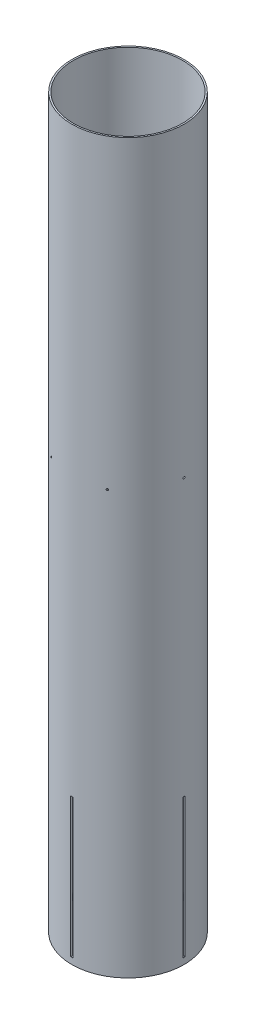
SolidWorks part; units mm, degrees
material "A-Glass Fiber"
ref_plane "Front Plane" through (0, 0, 0) normal (0, 0, 1) x (1, 0, 0)
ref_plane "Top Plane" through (0, 0, 0) normal (0, 1, 0) x (1, 0, 0)
ref_plane "Right Plane" through (0, 0, 0) normal (1, 0, 0) x (0, 0, -1)
sketch "Sketch1" plane through (0, 0, 0) normal (0, 1, 0) x (1, 0, 0)
  circle A0 centre (0, 0) radius 76.2
  circle A1 centre (0, 0) radius 78.359
  dimension "D1" = 152.4
  dimension "D2" = 156.718
extrude "Boss-Extrude1" add sketch "Sketch1" along normal blind 1016
ref_plane "Plane1" through (0, 0, 0) normal (0.7071, 0, 0.7071) x (0.7071, 0, -0.7071)
ref_axis "Axis1" through (0, 1016, 0) along (0, -1, 0)
sketch "Sketch2" plane through (0, 0, 0) normal (1, 0, 0) x (0, 0, -1)
  line L0 (0, 0) -> (0, 8.89)
  line L1 (1.5875, 8.89) -> (-1.5875, 8.89)
  line L2 (1.5875, 8.89) -> (1.5875, 203.2)
  line L3 (1.5875, 203.2) -> (-1.5875, 203.2)
  line L4 (-1.5875, 8.89) -> (-1.5875, 203.2)
  line L5 (1.5875, 8.89) -> (-1.5875, 203.2) construction
  line L6 (1.5875, 203.2) -> (-1.5875, 8.89) construction
  line L7 (78.359, 1016) -> (-78.359, 1016) construction
  line L8 (78.359, 1016) -> (-78.359, 1016)
  line L9 (0, 1016) -> (0, 588.645)
  line L10 (-78.359, 0) -> (78.359, 0) construction
  circle A0 centre (0, 588.645) radius 1.3525
  point P0 (0, 106.045)
  dimension "D4" = 2.7051
  dimension "D1" = 3.175
  dimension "D2" = 194.31
  dimension "D5" = 588.645
  dimension "D3" = 203.2
extrude "Cut-Extrude1" cut sketch "Sketch2" against normal through all contours L4 L1 L2 L3 region at (0, 106.045, 0)
pattern_circular "CirPattern1" count 4 over 360 about axis through (0, 0, 0) along (0, 1, 0) of "Cut-Extrude1" reverse direction yes
extrude "Cut-Extrude2" cut sketch "Sketch2<3>" against normal through all contours A0 region at (0, 587.7157, 0.9293)
sketch "Sketch2<3>" plane through (0, 0, 0) normal (1, 0, 0) x (0, 0, -1) same geometry as "Sketch2"
pattern_circular "CirPattern2" count 6 over 360 about axis through (0, 1016, 0) along (0, -1, 0) of "Cut-Extrude2"
sketch "Sketch3" plane through (0, 0, 0) normal (0.7071, 0, 0.7071) x (0.7071, 0, -0.7071)
  line L0 (0, 0) -> (0, 127) construction
  circle A0 centre (0, 127) radius 3.175
  dimension "D1" = 6.35
  dimension "D2" = 127
extrude "Cut-Extrude3" cut sketch "Sketch3" against normal through all
equation "\"Aft_Lower_Length\"= 22in"
equation "\"D1@Boss-Extrude1\" = \"Aft_Section_Length\""
equation "\"AB_Coupler_OD_Length\"= 1in"
equation "\"AB_Coupling_Section_Length\"= 0.375in"
equation "\"AB_Coupler_Length\"= \"AB_Coupler_OD_Length\" + \"AB_Coupling_Section_Length\" * 2"
equation "\"AB_Coupler_Num_Screws\"= 6"
equation "\"AB_Coupling_Screw_Diameter\"= 0.1065in"
equation "\"Aft_Section_Length\"= 40in"
equation "\"D4@Sketch2\"=\"AB_Coupling_Screw_Diameter\""
equation "\"D1@CirPattern2\"=\"AB_Coupler_Num_Screws\""
equation "\"Rail_Nut_From_Bottom\"= 5in"
equation "\"Rail_Nut_Diam\"= 0.25in"
equation "\"D1@Sketch3\"=\"Rail_Nut_Diam\""
equation "\"D2@Sketch3\"=\"Rail_Nut_From_Bottom\""
